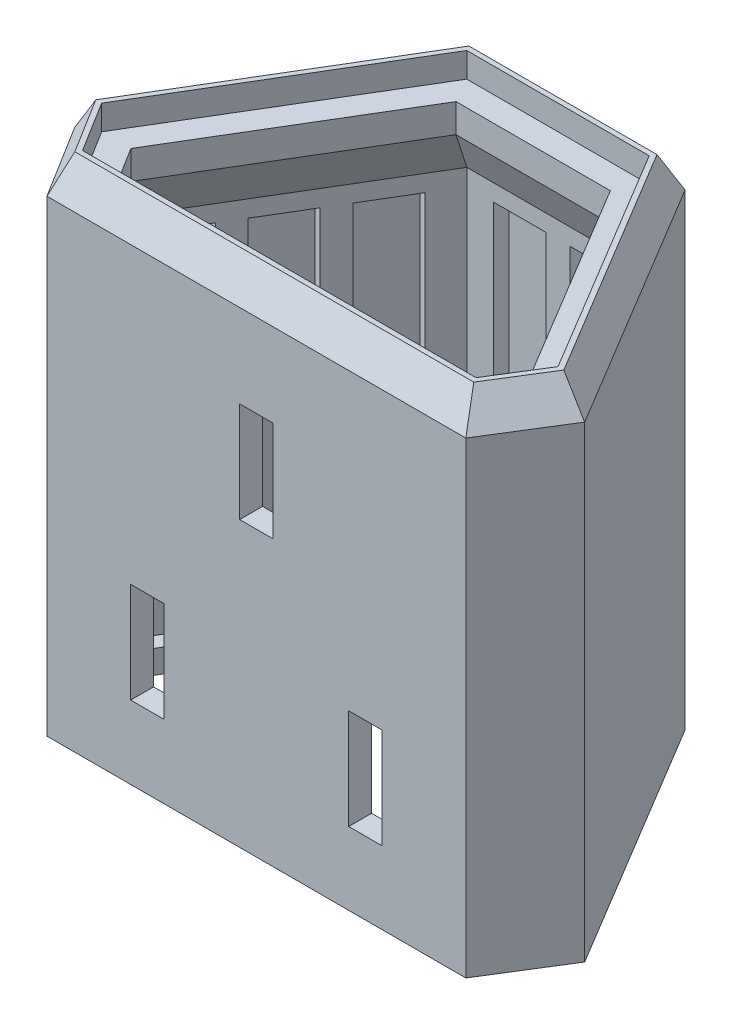
SolidWorks part; units mm, degrees
ref_plane "Front Plane" through (0, 0, 0) normal (0, 0, 1) x (1, 0, 0)
ref_plane "Top Plane" through (0, 0, 0) normal (0, 1, 0) x (1, 0, 0)
ref_plane "Right Plane" through (0, 0, 0) normal (1, 0, 0) x (0, 0, -1)
sketch "Sketch1" plane through (0, 0, 0) normal (0, 1, 0) x (1, 0, 0)
  line L0 (-26.953, -2.692) -> (-22.0553, -10.5661)
  line L1 (-23.906, -2.668) -> (-20.6106, -7.9661)
  line L2 (-20.6106, -7.9661) -> (20.6106, -7.9661)
  line L3 (20.6106, -7.9661) -> (23.906, -2.668)
  line L4 (23.906, -2.668) -> (9.5567, 21.2339)
  line L5 (9.5567, 21.2339) -> (-9.5567, 21.2339)
  line L6 (-9.5567, 21.2339) -> (-23.906, -2.668)
  line L7 (11.0283, 23.8339) -> (-11.0283, 23.8339)
  line L8 (-22.0553, -10.5661) -> (22.0553, -10.5661)
  line L9 (22.0553, -10.5661) -> (26.953, -2.692)
  line L10 (26.953, -2.692) -> (11.0283, 23.8339)
  line L11 (-11.0283, 23.8339) -> (-26.953, -2.692)
  dimension "D1" = 2.6
extrude "Boss-Extrude1" add sketch "Sketch1" along normal blind 52.6
sketch "Sketch2" plane through (0, 52.6, 0) normal (0, 1, 0) x (1, 0, 0)
  line L12 (-20.8591, -2.644) -> (-19.1659, -5.3661)
  line L13 (-19.1659, -5.3661) -> (19.1659, -5.3661)
  line L14 (19.1659, -5.3661) -> (20.8591, -2.644)
  line L15 (20.8591, -2.644) -> (8.085, 18.6339)
  line L16 (8.085, 18.6339) -> (-8.085, 18.6339)
  line L17 (-8.085, 18.6339) -> (-20.8591, -2.644)
  line L18 (-20.8591, -2.644) -> (-19.1659, -5.3661)
  line L19 (-19.1659, -5.3661) -> (19.1659, -5.3661)
  line L20 (19.1659, -5.3661) -> (20.8591, -2.644)
  line L21 (20.8591, -2.644) -> (8.085, 18.6339)
  line L22 (8.085, 18.6339) -> (-8.085, 18.6339)
  line L23 (-8.085, 18.6339) -> (-20.8591, -2.644)
  line L30 (-23.906, -2.668) -> (-20.6106, -7.9661)
  line L31 (-20.6106, -7.9661) -> (20.6106, -7.9661)
  line L32 (20.6106, -7.9661) -> (23.906, -2.668)
  line L33 (23.906, -2.668) -> (9.5567, 21.2339)
  line L34 (9.5567, 21.2339) -> (-9.5567, 21.2339)
  line L35 (-9.5567, 21.2339) -> (-23.906, -2.668)
  line L36 (-23.906, -2.668) -> (-20.6106, -7.9661)
  line L37 (-20.6106, -7.9661) -> (20.6106, -7.9661)
  line L38 (20.6106, -7.9661) -> (23.906, -2.668)
  line L39 (23.906, -2.668) -> (9.5567, 21.2339)
  line L40 (9.5567, 21.2339) -> (-9.5567, 21.2339)
  line L41 (-9.5567, 21.2339) -> (-23.906, -2.668)
  dimension "D1" = 2.6
  dimension "D2" = 0
extrude "Boss-Extrude2" add sketch "Sketch2" against normal blind 10.6
sketch "Sketch3" plane through (0, 52.6, 0) normal (0, 1, 0) x (1, 0, 0)
  line L6 (-23.906, -2.668) -> (-20.6106, -7.9661)
  line L7 (-20.6106, -7.9661) -> (20.6106, -7.9661)
  line L8 (20.6106, -7.9661) -> (23.906, -2.668)
  line L9 (23.906, -2.668) -> (9.5567, 21.2339)
  line L10 (9.5567, 21.2339) -> (-9.5567, 21.2339)
  line L11 (-9.5567, 21.2339) -> (-23.906, -2.668)
  line L12 (-20.8591, -2.644) -> (-19.1659, -5.3661)
  line L13 (-8.085, 18.6339) -> (-20.8591, -2.644)
  line L14 (-19.1659, -5.3661) -> (19.1659, -5.3661)
  line L15 (19.1659, -5.3661) -> (20.8591, -2.644)
  line L16 (20.8591, -2.644) -> (8.085, 18.6339)
  line L17 (8.085, 18.6339) -> (-8.085, 18.6339)
  line L18 (-20.8591, -2.644) -> (-19.1659, -5.3661)
  line L19 (-8.085, 18.6339) -> (-20.8591, -2.644)
  line L20 (-19.1659, -5.3661) -> (19.1659, -5.3661)
  line L21 (19.1659, -5.3661) -> (20.8591, -2.644)
  line L22 (20.8591, -2.644) -> (8.085, 18.6339)
  line L23 (8.085, 18.6339) -> (-8.085, 18.6339)
  dimension "D1" = 0
  dimension "D2" = 2.6
extrude "Cut-Extrude1" cut sketch "Sketch3" against normal blind 2.6
chamfer "Chamfer1" distance 4 distance2 2.08 6 edges at (-24.5042, 52.6, 6.6291) (-18.9907, 52.6, -10.5709) (0, 52.6, 10.5661) (24.5042, 52.6, 6.6291) (18.9907, 52.6, -10.5709) (0, 52.6, -23.8339) first distance on face at (-24.5042, 26.3, 6.6291) first distance on face at (-18.9907, 26.3, -10.5709) first distance on face at (0, 26.3, 10.5661) first distance on face at (24.5042, 26.3, 6.6291) first distance on face at (18.9907, 26.3, -10.5709) first distance on face at (0, 26.3, -23.8339)
chamfer "Chamfer2" distance 5 distance2 2.6 6 edges at (0, 42, -18.6339) (14.472, 42, -7.995) (20.0125, 42, 4.005) (0, 42, 5.3661) (-20.0125, 42, 4.005) (-14.472, 42, -7.995) first distance on face at (0, 46, -18.6339) first distance on face at (14.472, 46, -7.995) first distance on face at (20.0125, 46, 4.005) first distance on face at (0, 46, 5.3661) first distance on face at (-20.0125, 46, 4.005) first distance on face at (-14.472, 46, -7.995)
sketch "Sketch4" plane through (0, 0, 10.5661) normal (0, 0, 1) x (1, 0, 0)
  line L0 (13.1708, 8.3166) -> (-13.1708, 8.3166) construction
  line L1 (0, 18.1568) -> (0, 20.0526) construction
  line L3 (-1.75, 29.7442) -> (-1.75, 40.2442)
  line L4 (-1.75, 40.2442) -> (1.75, 40.2442)
  line L5 (1.75, 29.7442) -> (1.75, 40.2442)
  line L6 (-1.75, 29.7442) -> (1.75, 29.7442)
  line L7 (-13.1708, 7.6568) -> (-13.1708, 18.1568)
  line L8 (-13.1708, 18.1568) -> (-9.6708, 18.1568)
  line L9 (-9.6708, 7.6568) -> (-9.6708, 18.1568)
  line L10 (-12.1208, 7.6568) -> (-9.6708, 18.1568) construction
  line L11 (-13.1708, 18.1568) -> (-10.7208, 7.6568) construction
  line L13 (9.6708, 7.6076) -> (9.6708, 18.1076)
  line L14 (9.6708, 18.1076) -> (13.1708, 18.1076)
  line L15 (13.1708, 7.6076) -> (13.1708, 18.1076)
  line L16 (10.7208, 7.6076) -> (13.1708, 18.1076) construction
  line L17 (9.6708, 18.1076) -> (12.1208, 7.6076) construction
  line L18 (-0.7, 29.7442) -> (1.75, 40.2442) construction
  line L19 (-1.75, 40.2442) -> (0.7, 29.7442) construction
  line L21 (0, 10.6322) -> (0, 18.1568) construction
  line L22 (0, 10.6322) -> (0, -0.4208) construction
  line L25 (13.1708, 7.6076) -> (9.6708, 7.6076)
  line L26 (-9.6708, 7.6568) -> (-13.1708, 7.6568)
  dimension "D1" = 3.5
  dimension "D3" = 3.5
  dimension "D5" = 3.5
  dimension "D8" = 0
extrude "Cut-Extrude2" cut sketch "Sketch4" against normal blind 10
sketch "Sketch6" plane through (0, 0, 0) normal (0, -1, 0) x (1, 0, 0)
  line L12 (11.0283, -23.8339) -> (26.953, 2.692)
  line L13 (26.953, 2.692) -> (22.0553, 10.5661)
  line L14 (22.0553, 10.5661) -> (-22.0553, 10.5661)
  line L15 (-22.0553, 10.5661) -> (-26.953, 2.692)
  line L16 (-26.953, 2.692) -> (-11.0283, -23.8339)
  line L17 (-11.0283, -23.8339) -> (11.0283, -23.8339)
  line L18 (11.0283, -23.8339) -> (26.953, 2.692)
  line L19 (26.953, 2.692) -> (22.0553, 10.5661)
  line L20 (22.0553, 10.5661) -> (-22.0553, 10.5661)
  line L21 (-22.0553, 10.5661) -> (-26.953, 2.692)
  line L22 (-26.953, 2.692) -> (-11.0283, -23.8339)
  line L23 (-11.0283, -23.8339) -> (11.0283, -23.8339)
  line L30 (10.9151, -23.6339) -> (26.7186, 2.6902)
  line L31 (26.7186, 2.6902) -> (21.9442, 10.3661)
  line L32 (21.9442, 10.3661) -> (-21.9442, 10.3661)
  line L33 (-21.9442, 10.3661) -> (-26.7186, 2.6902)
  line L34 (-26.7186, 2.6902) -> (-10.9151, -23.6339)
  line L35 (-10.9151, -23.6339) -> (10.9151, -23.6339)
  line L36 (10.9151, -23.6339) -> (26.7186, 2.6902)
  line L37 (26.7186, 2.6902) -> (21.9442, 10.3661)
  line L38 (21.9442, 10.3661) -> (-21.9442, 10.3661)
  line L39 (-21.9442, 10.3661) -> (-26.7186, 2.6902)
  line L40 (-26.7186, 2.6902) -> (-10.9151, -23.6339)
  line L41 (-10.9151, -23.6339) -> (10.9151, -23.6339)
  dimension "D1" = 0
  dimension "D2" = 0.2
extrude "Cut-Extrude3" cut sketch "Sketch6" against normal blind 61
sketch "Sketch7" plane through (0, 0, 7.9661) normal (0, 0, -1) x (-1, 0, 0)
  line L4 (-2.7242, 2.4442) -> (2.7758, 2.4442)
  line L5 (-2.7242, 2.4442) -> (-2.7242, 40.2442)
  line L6 (-2.7242, 40.2442) -> (2.7758, 40.2442)
  line L7 (2.7758, 2.4442) -> (2.7758, 40.2442)
  line L8 (-2.7242, 2.4442) -> (2.7758, 40.2442) construction
  line L11 (-2.7242, 40.2442) -> (2.7758, 2.4442) construction
  point P4 (0.0258, 21.3442)
  dimension "D1" = 5.5
  dimension "D2" = 37.8
extrude "Cut-Extrude4" cut sketch "Sketch7" against normal blind 1.6
pattern_linear "LPattern1" count 3 spacing 8 along (-1, 0, 0) count 3 spacing 8 along (1, 0, 0) of "Cut-Extrude4"
sketch "Sketch8" plane through (0, 0, 9.5661) normal (0, 0, -1) x (-1, 0, 0)
  line L0 (2.7758, 40.2442) -> (2.7758, 28.4546)
  line L1 (2.7758, 2.4442) -> (2.7758, 40.2442) construction
  line L2 (2.7758, 28.4546) -> (-2.7242, 28.4546)
  line L3 (-2.7242, 40.2442) -> (-2.7242, 2.4442) construction
  line L4 (-2.7242, 28.4546) -> (-2.7242, 40.2442)
  line L5 (-2.7242, 40.2442) -> (-1.75, 40.2442)
  line L6 (-1.75, 40.2442) -> (-1.75, 29.7442)
  line L7 (-1.75, 29.7442) -> (1.75, 29.7442)
  line L8 (1.75, 29.7442) -> (1.75, 40.2442)
  line L9 (1.75, 40.2442) -> (2.7758, 40.2442)
extrude "Boss-Extrude4" add sketch "Sketch8" along normal blind 1.6
sketch "Sketch9" plane through (0, 0, 9.5661) normal (0, 0, -1) x (-1, 0, 0)
  line L0 (10.7758, 18.1568) -> (9.6708, 18.1568)
  line L1 (9.6708, 18.1568) -> (9.6708, 7.6568) construction
  line L2 (10.7758, 18.1568) -> (9.6708, 18.1568) construction
  line L3 (9.6708, 18.1568) -> (9.6708, 7.6568)
  line L4 (9.6708, 7.6568) -> (10.7758, 7.6568)
  line L5 (10.7758, 7.6568) -> (10.7758, 6.4266)
  line L6 (10.7758, 2.4442) -> (10.7758, 7.6568) construction
  line L7 (10.7758, 6.4266) -> (8.5312, 6.4266)
  line L8 (8.5312, 6.4266) -> (8.5312, 19.4147)
  line L9 (8.5312, 19.4147) -> (10.7758, 19.4147)
  line L10 (10.7758, 18.1568) -> (10.7758, 40.2442) construction
  line L11 (10.7758, 19.4147) -> (10.7758, 18.1568)
  line L12 (13.2758, 19.4147) -> (14.4162, 19.4147)
  line L13 (13.2758, 40.2442) -> (13.2758, 2.4442) construction
  line L14 (14.4162, 19.4147) -> (14.4162, 6.4266)
  line L15 (14.4162, 6.4266) -> (13.2758, 6.4266)
  line L16 (13.2758, 40.2442) -> (13.2758, 2.4442) construction
  line L17 (13.2758, 19.4147) -> (13.2758, 6.4266)
extrude "Boss-Extrude5" add sketch "Sketch9" along normal blind 1.6
sketch "Sketch11" plane through (0, 0, 9.5661) normal (0, 0, -1) x (-1, 0, 0)
  line L0 (-10.7242, 18.1076) -> (-9.6708, 18.1076)
  line L1 (-9.6708, 18.1076) -> (-9.6708, 7.6076)
  line L2 (-9.6708, 7.6076) -> (-10.7242, 7.6076)
  line L3 (14.4162, 6.4266) -> (-16.0355, 6.4266) construction
  line L4 (14.4162, 19.4147) -> (-18.1166, 19.4147) construction
  line L5 (14.4162, 19.4147) -> (13.2758, 19.4147) construction
  line L6 (-10.7242, 18.1076) -> (-10.7242, 19.4147)
  line L7 (-10.7242, 40.2442) -> (-10.7242, 18.1076) construction
  line L8 (-10.7242, 19.4147) -> (-8.5666, 19.4147)
  line L9 (-8.5666, 19.4147) -> (-8.5666, 6.4266)
  line L10 (-8.5666, 6.4266) -> (-10.7242, 6.4266)
  line L11 (-10.7242, 7.6076) -> (-10.7242, 2.4442) construction
  line L12 (-10.7242, 6.4266) -> (-10.7242, 7.6076)
  line L13 (-13.1708, 18.1076) -> (-13.2242, 19.4147)
  line L14 (-13.2242, 2.4442) -> (-13.2242, 40.2442) construction
  line L15 (-13.2242, 19.4147) -> (-14.3794, 19.4147)
  line L16 (-14.3794, 19.4147) -> (-14.3794, 6.4266)
  line L17 (-14.3794, 6.4266) -> (-13.1708, 6.4266)
  line L19 (-13.1708, 6.4266) -> (-13.1708, 18.1076)
extrude "Boss-Extrude6" add sketch "Sketch11" along normal blind 1.6
sketch "Sketch12" plane through (0, 0, 9.5661) normal (0, 0, -1) x (-1, 0, 0)
  line L0 (2.7758, 19.4147) -> (-2.7242, 19.4147)
  line L1 (2.7758, 2.4442) -> (2.7758, 28.4546) construction
  line L2 (-2.7242, 28.4546) -> (-2.7242, 2.4442) construction
  line L3 (2.7758, 18.1568) -> (-2.7242, 18.1568)
  line L4 (-2.7242, 18.1568) -> (-2.7242, 19.4147)
  line L5 (2.7758, 18.1568) -> (2.7758, 19.4147)
extrude "Boss-Extrude7" add sketch "Sketch12" along normal blind 1.6
sketch "Sketch13" plane through (18.4337, 0, 11.4659) normal (-0.8491, 0, -0.5282) x (-0.5282, 0, 0.8491)
  line L0 (-7.2413, 42) -> (-7.2413, 0) construction
  line L1 (-4.1216, 42) -> (-10.361, 42) construction
  line L2 (-4.1216, 0) -> (-10.361, 0) construction
  line L3 (-4.992, 2.4442) -> (-9.4906, 2.4442)
  line L5 (-9.4906, 2.4442) -> (-9.4906, 40.2442)
  line L6 (-9.4906, 40.2442) -> (-4.992, 40.2442)
  line L7 (-4.992, 2.4442) -> (-4.992, 40.2442)
  line L8 (-9.4101, 2.4442) -> (-4.992, 40.2442) construction
  line L9 (-9.4906, 40.2442) -> (-5.0725, 2.4442) construction
  point P6 (-7.2413, 21)
extrude "Cut-Extrude5" cut sketch "Sketch13" against normal blind 1.6
sketch "Sketch14" plane through (0, 0, 7.9661) normal (0, 0, -1) x (-1, 0, 0)
  line L0 (-14.3794, 12.2298) -> (-14.3794, 13.4855)
  line L1 (-14.3794, 19.4147) -> (-14.3794, 6.4266) construction
  line L3 (-14.3794, 13.4855) -> (-18.7242, 13.4855)
  line L4 (-18.7242, 40.2442) -> (-18.7242, 2.4442) construction
  line L5 (-18.7242, 13.4855) -> (-18.7242, 12.2298)
  line L6 (-18.7242, 40.2442) -> (-18.7242, 2.4442) construction
  line L7 (-18.7242, 12.2298) -> (-14.3794, 12.2298)
  line L8 (14.4162, 12.2787) -> (14.4162, 13.535)
  line L9 (14.4162, 6.4266) -> (14.4162, 19.4147) construction
  line L10 (14.4162, 13.535) -> (18.7758, 13.535)
  line L11 (18.7758, 2.4442) -> (18.7758, 40.2442) construction
  line L12 (18.7758, 13.535) -> (18.7758, 12.2787)
  line L13 (18.7758, 12.2787) -> (14.4162, 12.2787)
  point P5 (-14.3794, 12.8576)
  point P7 (-14.3794, 12.8576)
  point P17 (14.4162, 12.9068)
extrude "Boss-Extrude8" add sketch "Sketch14" against normal blind 1.6
sketch "Sketch15" plane through (-18.4337, 0, 11.4659) normal (0.8491, 0, -0.5282) x (-0.5282, 0, -0.8491)
  line L0 (7.2413, 42) -> (7.2413, 0) construction
  line L1 (10.361, 42) -> (4.1216, 42) construction
  line L2 (10.361, 0) -> (4.1216, 0) construction
  line L4 (4.992, 40.2442) -> (9.492, 40.2442)
  line L5 (4.992, 40.2442) -> (4.992, 2.4442)
  line L6 (4.992, 2.4442) -> (9.492, 2.4442)
  line L7 (9.492, 40.2442) -> (9.492, 2.4442)
  dimension "D1" = 4.5
extrude "Cut-Extrude6" cut sketch "Sketch15" against normal blind 1.6
sketch "Sketch16" plane through (-16.3953, 0, -9.8428) normal (0.8574, 0, 0.5147) x (0.5147, 0, -0.8574)
  line L0 (-0.653, 42) -> (-0.653, 0) construction
  line L1 (13.2863, 42) -> (-14.5922, 42) construction
  line L2 (13.2863, 0) -> (-14.5922, 0) construction
  line L3 (-3.403, 2.4442) -> (2.097, 2.4442)
  line L5 (2.097, 2.4442) -> (2.097, 40.2442)
  line L6 (2.097, 40.2442) -> (-3.403, 40.2442)
  line L7 (-3.403, 2.4442) -> (-3.403, 40.2442)
  line L8 (1.9987, 2.4442) -> (-3.403, 40.2442) construction
  line L9 (2.097, 40.2442) -> (-3.3046, 2.4442) construction
  point P6 (-0.653, 21)
  dimension "D1" = 5.5
extrude "Cut-Extrude7" cut sketch "Sketch16" against normal blind 1.6
pattern_linear "LPattern2" count 2 spacing 8 along (-0.5147, 0, 0.8574) count 2 spacing 8 along (0.5147, 0, -0.8574) of "Cut-Extrude7"
mirror "Mirror2" about plane through (0, 0, 0) normal (1, 0, 0) of "Cut-Extrude7", "LPattern2"
sketch "Sketch17" plane through (0, 0, -21.2339) normal (0, 0, 1) x (1, 0, 0)
  line L0 (0, 42) -> (0, 0) construction
  line L1 (9.5567, 42) -> (-9.5567, 42) construction
  line L2 (0, 21) -> (1.25, 21) construction
  line L3 (1.25, 21) -> (4, 21) construction
  line L4 (6.75, 2.4442) -> (1.25, 2.4442)
  line L6 (1.25, 2.4442) -> (1.25, 40.2442)
  line L7 (1.25, 40.2442) -> (6.75, 40.2442)
  line L8 (6.75, 2.4442) -> (6.75, 40.2442)
  line L9 (1.3484, 2.4442) -> (6.75, 40.2442) construction
  line L10 (1.25, 40.2442) -> (6.6516, 2.4442) construction
  dimension "D1" = 5.5
extrude "Cut-Extrude8" cut sketch "Sketch17" against normal blind 1.6
pattern_linear "LPattern3" count 2 spacing 8 along (-1, 0, 0) of "Cut-Extrude8"
